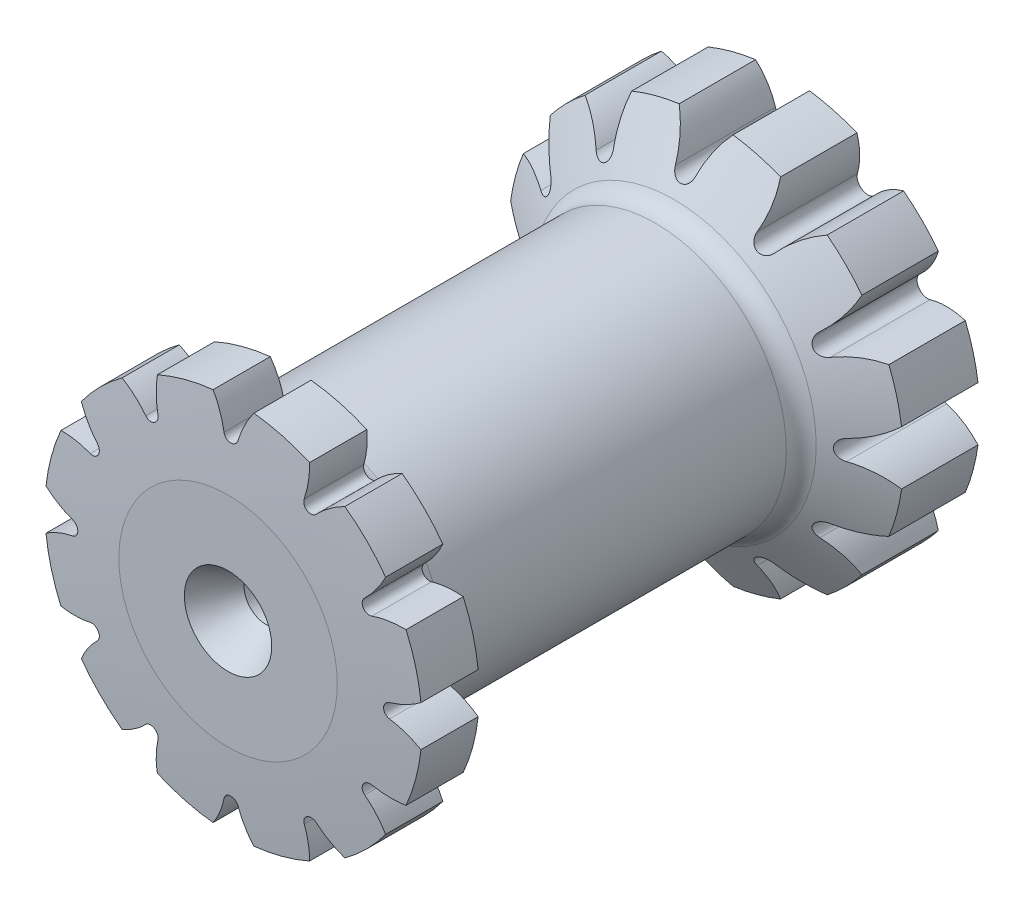
SolidWorks part; units mm, degrees
material "EN39B"
ref_plane "Front Plane" through (0, 0, 0) normal (0, 0, 1) x (1, 0, 0)
ref_plane "Top Plane" through (0, 0, 0) normal (0, 1, 0) x (1, 0, 0)
ref_plane "Right Plane" through (0, 0, 0) normal (1, 0, 0) x (0, 0, -1)
sketch "Sketch1" plane through (0, 0, 0) normal (1, 0, 0) x (0, 0, -1)
  line L0 (0, 0) -> (47.2544, 0) construction
  line L1 (0.3724, 12.95) -> (4.3, 12.95)
  line L2 (4.3, 12.95) -> (4.3, 10.5)
  line L3 (5.8, 9) -> (29.334, 9)
  line L4 (30.633, 9.75) -> (32.8269, 13.55)
  line L5 (32.8269, 13.55) -> (38.0744, 13.55)
  line L6 (38.5, 0) -> (38.5, 7.5)
  line L7 (0, 0) -> (0, 7.5)
  line L8 (0, 0) -> (38.5, 0)
  arc A0 (0, 7.5) -> (0.3724, 12.95) centre (149.8124, 0) cw
  arc A1 (38.5, 7.5) -> (38.0744, 13.55) centre (-111.3124, 0) ccw
  arc A2 (4.3, 10.5) -> (5.8, 9) centre (5.8, 10.5) ccw
  arc A3 (29.334, 9) -> (30.633, 9.75) centre (29.334, 10.5) ccw
  point P18 (30.2, 9)
  dimension "D7" = 150
  dimension "D8" = 15
  dimension "D10" = 150
  dimension "D12" = 1.5
  dimension "D1" = 27.1
  dimension "D2" = 25.9
  dimension "D3" = 4.3
  dimension "D4" = 8.3
  dimension "D5" = 60
  dimension "D6" = 18
  dimension "D9" = 38.5
  dimension "D11" = 15
revolve "Revolve1" add sketch "Sketch1" angle 360 about L0
sketch "Sketch2" plane through (0, 0, 0) normal (1, 0, 0) x (0, 0, -1)
  line L0 (38.5, 3) -> (35.9019, 1.5)
  line L1 (35.9019, 1.5) -> (33.4013, 1.5)
  line L2 (33.4013, 1.5) -> (32.5, 0)
  line L3 (0, 0) -> (41.5, 0) construction
  line L4 (38.5, -7.5) -> (38.5, 7.5) construction
  line L5 (38.5, 3) -> (38.5, 0)
  line L6 (32.5, 0) -> (38.5, 0)
  dimension "D1" = 3
  dimension "D2" = 30
  dimension "D3" = 59
  dimension "D4" = 6
  dimension "D5" = 6
revolve "Cut-Revolve1" cut sketch "Sketch2" angle 360 about L3
sketch "Sketch3" plane through (0, 0, 0) normal (1, 0, 0) x (0, 0, -1)
  line L0 (0, 3) -> (2.5981, 1.5)
  line L1 (2.5981, 1.5) -> (5.0987, 1.5)
  line L2 (5.0987, 1.5) -> (6, 0)
  line L3 (0, 3) -> (0, 0)
  line L4 (0, 0) -> (12.7492, 0) construction
  line L5 (6, 0) -> (0, 0)
  dimension "D1" = 6
  dimension "D2" = 30
  dimension "D3" = 59
  dimension "D4" = 3
  dimension "D5" = 6
revolve "Cut-Revolve2" cut sketch "Sketch3" angle 360 about L4
ref_plane "Plane1" through (0, 0, -40) normal (0, 0, 1) x (1, 0, 0)
sketch "Sketch4" plane through (0, 0, -40) normal (0, 0, 1) x (1, 0, 0)
  line L0 (0, 0) -> (-15.7466, 0) construction
  line L1 (0, 0) -> (0, 14.7663) construction
  arc A0 (-0.6871, 11.0661) -> (0.6871, 11.0661) centre (0, 11.2) ccw
  circle A1 centre (0, 0) radius 13.55 construction
  arc A2 (1.85, 13.4231) -> (-1.85, 13.4231) centre (0, 0) ccw
  arc A3 (-1.85, 13.4231) -> (-0.6871, 11.0661) centre (-5.5948, 10.1101) cw
  arc A4 (1.85, 13.4231) -> (0.6871, 11.0661) centre (5.5948, 10.1101) ccw
  dimension "D1" = 1.4
  dimension "D3" = 21
  dimension "D4" = 5
  dimension "D2" = 3.7
extrude "Cut-Extrude1" cut sketch "Sketch4" along normal up to surface (7.1731 mm away) up to face at (9.75, 0, -30.633)
ref_axis "Axis1" through (0, 0, -29.334) along (0, 0, 1)
pattern_circular "CirPattern1" count 12 over 360 about axis through (0, 0, -29.334) along (0, 0, 1) of "Cut-Extrude1"
sketch "Sketch5" plane through (0, 0, 0) normal (0, 0, 1) x (1, 0, 0)
  line L0 (0, 0) -> (20.7288, 0) construction
  line L1 (0, 0) -> (0, 13.7027) construction
  circle A0 centre (0, 0) radius 12.95 construction
  arc A1 (1.4, 12.8741) -> (-1.4, 12.8741) centre (0, 0) ccw
  arc A2 (-0.4857, 10.8812) -> (0.4857, 10.8812) centre (0, 11) ccw
  arc A3 (1.4, 12.8741) -> (0.4857, 10.8812) centre (6.1195, 9.5027) ccw
  arc A4 (-1.4, 12.8741) -> (-0.4857, 10.8812) centre (-6.1195, 9.5027) cw
  dimension "D1" = 1
  dimension "D3" = 21
  dimension "D4" = 5.8
  dimension "D2" = 2.8
extrude "Cut-Extrude2" cut sketch "Sketch5" against normal up to surface (4.3 mm away) up to face at (12.95, 0, -4.3)
pattern_circular "CirPattern2" count 12 over 360 about axis through (0, 0, -29.334) along (0, 0, 1) of "Cut-Extrude2"
